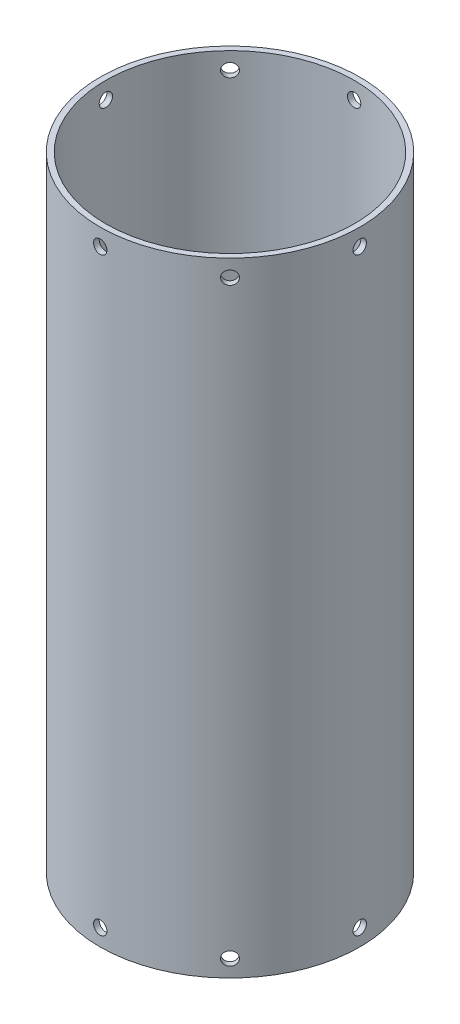
SolidWorks part; units mm, degrees
material "6061-T6 (SS)"
ref_plane "Front Plane" through (0, 0, 0) normal (0, 0, 1) x (1, 0, 0)
ref_plane "Top Plane" through (0, 0, 0) normal (0, 1, 0) x (1, 0, 0)
ref_plane "Right Plane" through (0, 0, 0) normal (1, 0, 0) x (0, 0, -1)
sketch "Sketch1" plane through (0, 0, 0) normal (0, 1, 0) x (1, 0, 0)
  circle A0 centre (0, 0) radius 97.5246
  circle A1 centre (0, 0) radius 93.2985
  dimension "D1" = 195.0491
  dimension "D2" = 4.2261
extrude "Boss-Extrude1" add sketch "Sketch1" along normal blind 467.995
sketch "Sketch2" [suppressed] plane through (0, 667.7406, 0) normal (1, 0, 0) x (0, 0, 1)
  circle A0 centre (0, -12.7) radius 4.7625 construction
  circle A1 centre (0, -12.7) radius 4.7625 construction
  circle A2 centre (0, -12.7) radius 5.0165
  dimension "D1" = 0.254
extrude "LOX Top Holes" [suppressed] cut sketch "Sketch2" along normal up to surface (76.0347 mm away) contours A2
pattern_circular "CirPattern1" [suppressed] count 8 over 360
sketch "Sketch3" [suppressed] plane through (0, 25.4, 0) normal (1, 0, 0) x (0, 0, -1)
  circle A0 centre (0, -12.7) radius 4.7625 construction
  circle A1 centre (0, -12.7) radius 4.7625 construction
  circle A2 centre (0, -12.7) radius 5.0165
  dimension "D1" = 0.254
extrude "LOX Bottom Holes" [suppressed] cut sketch "Sketch3" along normal up to surface (76.0347 mm away) contours A2
pattern_circular "CirPattern2" [suppressed] count 8 over 360
sketch "Sketch4" plane through (0, 442.595, 0) normal (1, 0, 0) x (0, 0, 1)
  circle A0 centre (0, -12.7) radius 4.7625 construction
  circle A1 centre (0, -12.7) radius 4.7625 construction
  circle A2 centre (0, -12.7) radius 5.0165
  dimension "D1" = 0.254
extrude "Cut-Extrude1" cut sketch "Sketch4" along normal up to surface (97.3955 mm away) contours A2
pattern_circular "CirPattern3" count 8 over 360 about axis through (0, 467.995, 0) along (0, 1, 0) of "Cut-Extrude1"
sketch "Sketch7" plane through (0, 25.4, 0) normal (1, 0, 0) x (0, 0, -1)
  circle A0 centre (0, -12.7) radius 4.7625 construction
  circle A1 centre (0, -12.7) radius 4.7625 construction
  circle A2 centre (0, -12.7) radius 5.0165
  dimension "D1" = 0.254
extrude "Cut-Extrude2" cut sketch "Sketch7" along normal up to surface (97.3955 mm away)
pattern_circular "CirPattern4" count 8 over 360 about axis through (0, 0, 0) along (0, 1, 0) of "Cut-Extrude2"
scale "Scale1" scale about centroid uniform scaling yes scale factor 0.390667
